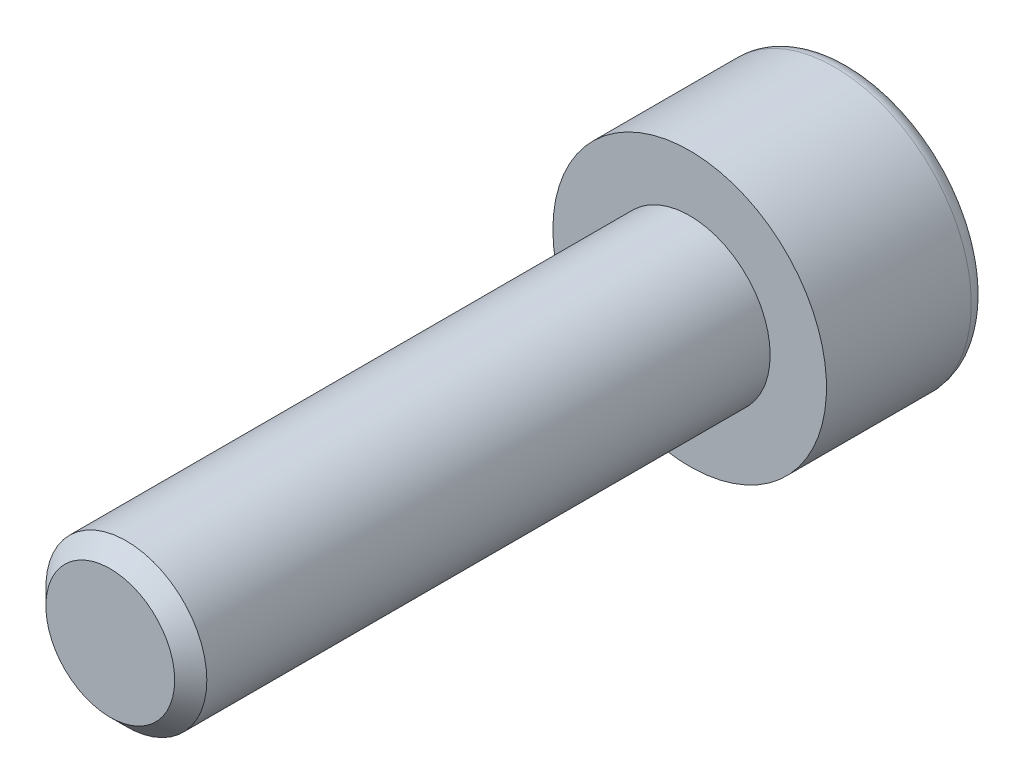
SolidWorks part; units mm, degrees
ref_plane "Plan1" through (0, 0, 0) normal (0, 0, 1) x (1, 0, 0)
ref_plane "Plan2" through (0, 0, 0) normal (0, 1, 0) x (1, 0, 0)
ref_plane "Plan3" through (0, 0, 0) normal (1, 0, 0) x (0, 0, -1)
ref_axis "Z Axis" through (0, 0, -50) along (0, 0, 1)
sketch "Esquisse1" plane through (0, 0, 0) normal (0, 1, 0) x (1, 0, 0)
  line L0 (0, 0) -> (0, 5) construction
  line L1 (0, 0) -> (4.25, 0)
  line L2 (0, 0) -> (0, 5)
  line L3 (0, 5) -> (3.75, 5)
  line L5 (4.25, 0) -> (4.25, 4.5)
  arc A0 (3.75, 5) -> (4.25, 4.5) centre (3.75, 4.5) cw
  dimension "D3" = 0.5
  dimension "D1" = 4.25
  dimension "D2" = 5
revolve "Base-Révolution" add sketch "Esquisse1" angle 360 about L0 reverse direction yes
sketch "Esquisse2" plane through (0, 0, -5) normal (0, 0, 1) x (1, 0, 0)
  line L0 (2, -1.1547) -> (2, 1.1547)
  line L1 (0, 0) -> (2, 1.1547) construction
  line L2 (1, 0) -> (2, 0) construction
  line L3 (0, 2.3094) -> (2, 1.1547)
  line L4 (0, -2.3094) -> (2, -1.1547)
  line L5 (0, 0) -> (0, 2) construction
  line L6 (-2, -1.1547) -> (-2, 1.1547)
  line L7 (0, 2.3094) -> (-2, 1.1547)
  line L8 (0, -2.3094) -> (-2, -1.1547)
  circle A0 centre (0, 0) radius 2 construction
  dimension "D2" = 30
  dimension "D1" = 4
extrude "enlev-mat-Extru1" cut sketch "Esquisse2" along normal blind 2.5
sketch "Esquisse3" plane through (0, 0, 0) normal (0, 1, 0) x (1, 0, 0)
  line L1 (0, 0) -> (0, -18) construction
  line L2 (0, 0) -> (2.5, 0)
  line L3 (0, 0) -> (0, -18)
  line L4 (0, -18) -> (2.5, -18)
  line L6 (2.5, 0) -> (2.5, -18)
  dimension "D1" = 18
  dimension "D2" = 2.5
revolve "Boss.-Révol.1" add sketch "Esquisse3" angle 360 about L1 reverse direction yes
cosmetic thread "Représentation de filetage1" parameters "D1"=16, "D2"=4.2
sketch "Esquisse4" plane through (0, 0, 0) normal (0, 1, 0) x (1, 0, 0)
  line L0 (2.012, -18.0488) -> (2.012, -17.9512)
  line L1 (-2.5, -18) -> (2.5, -18) construction
  line L2 (2.012, -17.9512) -> (2.5488, -17.6413)
  line L3 (2.012, -18.0488) -> (2.5488, -18.3587)
  line L4 (2.5488, -17.6413) -> (2.5488, -18.3587)
  line L5 (2.5, -18) -> (2.5, 0) construction
  point P4 (2.5, -18)
  dimension "D2" = 0.0488
  dimension "D3" = 0.0488
  dimension "D4" = 0.5368
  dimension "D5" = 60
  dimension "D1" = 0.488
  dimension "D6" = 60
chamfer "Chanfrein1" distance 0.5 angle 45 1 edges at (2.5, 0, 18)
sketch "Esquisse5" plane through (0, 0, 18) normal (0, 0, 1) x (1, 0, 0)
  circle A0 centre (0, 0) radius 2.5 construction
  circle A1 centre (0, 0) radius 2.5
curve "Hélice1" pitch 0.8 height 16 turns 20
sweep "Enlèvement de matière-Balayage1" [suppressed] cut profiles "Esquisse4" path "Hélice1"
equation "\"D3@Esquisse1\"=\"D2@Esquisse1\"/10"
equation "\"D1@Chanfrein1\"=\"D2@Esquisse3\"*0.2"
equation "\"D3@Esquisse4\"=0.1*\"D1@Esquisse4\""
equation "\"D4@Esquisse4\"=1.1*\"D1@Esquisse4\""
equation "\"D2@Esquisse4\"=0.1*\"D1@Esquisse4\""
equation "\"D1@Esquisse4\"=0.61*\"D4@Hélice1\""
